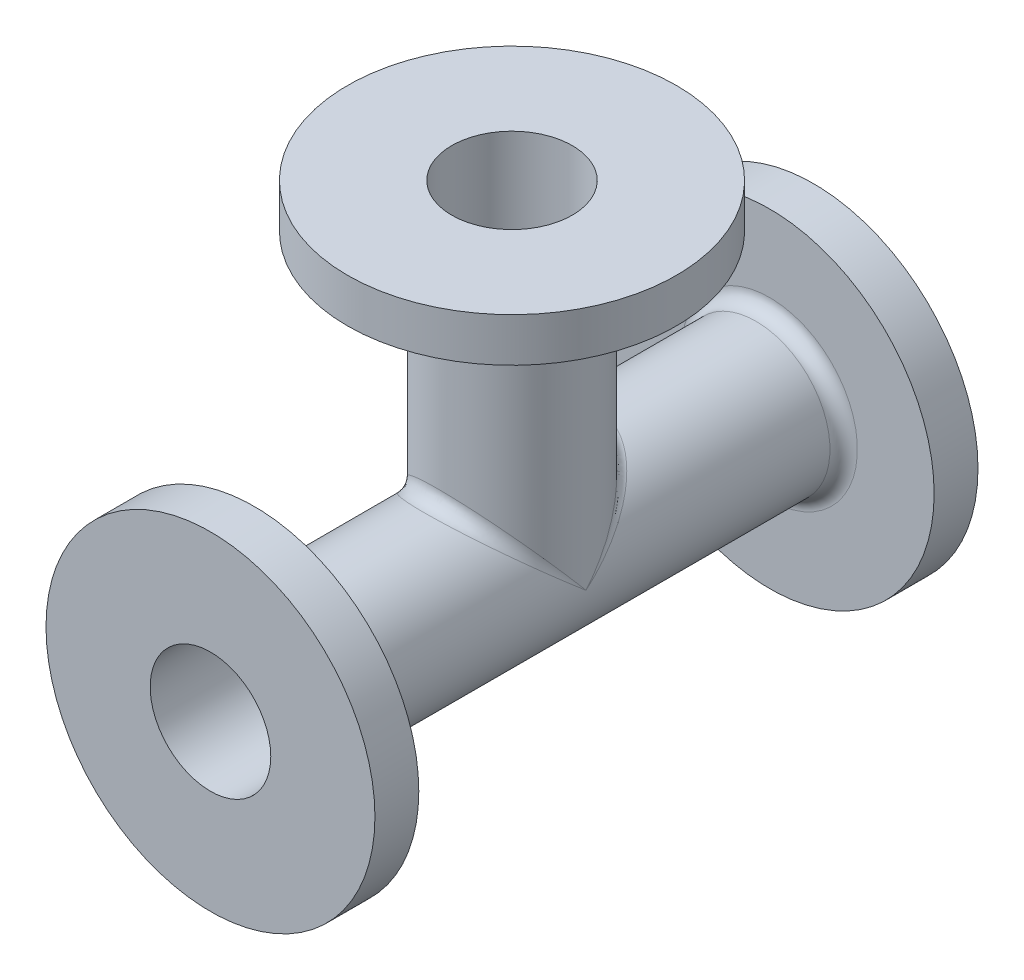
SolidWorks part; units mm, degrees
ref_plane "Front Plane" through (0, 0, 0) normal (0, 0, 1) x (1, 0, 0)
ref_plane "Top Plane" through (0, 0, 0) normal (0, 1, 0) x (1, 0, 0)
ref_plane "Right Plane" through (0, 0, 0) normal (1, 0, 0) x (0, 0, -1)
sketch "Sketch1" plane through (0, 0, 0) normal (0, 0, 1) x (1, 0, 0)
  line L0 (0, 70.4203) -> (0, -83.0959) construction
  line L1 (-121.1229, 0) -> (129.9254, 0) construction
  circle A0 centre (0, 0) radius 27
  circle A1 centre (0, 0) radius 22
  dimension "D1" = 54
  dimension "D2" = 44
extrude "Boss-Extrude1" add sketch "Sketch1" along normal mid plane 188
sketch "Sketch2" plane through (0, 0, 94) normal (0, 0, 1) x (1, 0, 0)
  circle A0 centre (0, 0) radius 22
  circle A1 centre (0, 0) radius 60
  dimension "D1" = 120
extrude "Boss-Extrude2" add sketch "Sketch2" along normal blind 16
mirror "Mirror1" about plane through (0, 0, 0) normal (0, 0, 1) of "Boss-Extrude2"
ref_plane "Plane1" through (0, 100, 0) normal (0, 1, 0) x (1, 0, 0)
sketch "Sketch3" plane through (0, 100, 0) normal (0, 1, 0) x (1, 0, 0)
  circle A0 centre (0, 0) radius 27
  circle A1 centre (0, 0) radius 22
  dimension "D1" = 54
  dimension "D2" = 44
extrude "Boss-Extrude3" add sketch "Sketch3" against normal up to surface (73 mm away) up to face at (27, 0, 94)
sketch "Sketch4" plane through (0, 100, 0) normal (0, 1, 0) x (1, 0, 0)
  circle A0 centre (0, 0) radius 22
extrude "Cut-Extrude5" cut sketch "Sketch4" along a picked direction on the side against the normal blind 100
sketch "Sketch6" plane through (0, 100, 0) normal (0, 1, 0) x (1, 0, 0)
  circle A0 centre (0, 0) radius 22
  circle A1 centre (0, 0) radius 60
  dimension "D1" = 120
  dimension "D2" = 44
extrude "Boss-Extrude4" add sketch "Sketch6" along normal blind 16
fillet "Fillet2" radius 5 5 edges at (-27, 0, -94) (0, 27, -27) (0, 27, 27) (0, 100, 27) (27, 0, 94)
